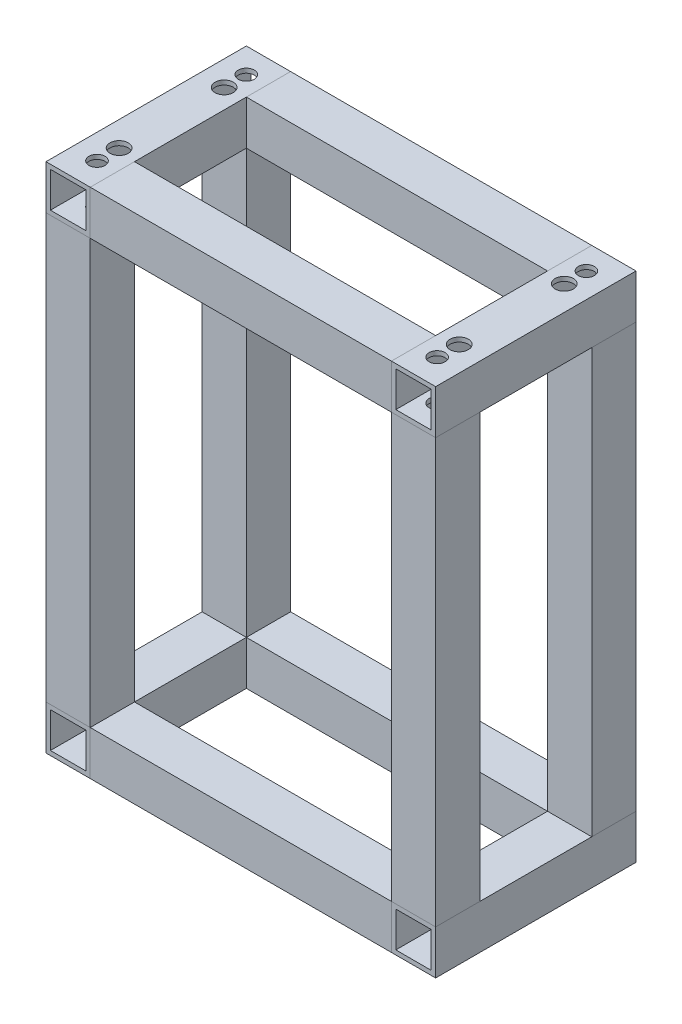
SolidWorks part; units mm, degrees
ref_plane "Front Plane" through (0, 0, 0) normal (0, 0, 1) x (1, 0, 0)
ref_plane "Top Plane" through (0, 0, 0) normal (0, 1, 0) x (1, 0, 0)
ref_plane "Right Plane" through (0, 0, 0) normal (1, 0, 0) x (0, 0, -1)
sketch "Sketch1" plane through (0, 0, 0) normal (0, 1, 0) x (1, 0, 0)
  line L1 (-111.887, 57.531) -> (111.887, 57.531)
  line L2 (-111.887, 57.531) -> (-111.887, -57.531)
  line L3 (-111.887, -57.531) -> (111.887, -57.531)
  line L4 (111.887, 57.531) -> (111.887, -57.531)
  line L5 (-111.887, 57.531) -> (111.887, -57.531) construction
  line L6 (-111.887, -57.531) -> (111.887, 57.531) construction
  point P0 (0, 0)
  dimension "D1" = 115.062
  dimension "D2" = 223.774
sketch "Sketch2" plane through (0, 0, 0) normal (0, 0, 1) x (1, 0, 0)
  line L0 (-111.887, 0) -> (111.887, 0) construction
  line L1 (-111.887, 0) -> (-86.487, 0)
  line L2 (-111.887, 0) -> (-111.887, -25.4)
  line L3 (-111.887, -25.4) -> (-86.487, -25.4)
  line L4 (-86.487, 0) -> (-86.487, -25.4)
  line L5 (-111.887, 0) -> (111.887, 0) construction
  line L6 (0, 0) -> (0, -45.1999) construction
  line L7 (111.887, -25.4) -> (86.487, -25.4)
  line L8 (86.487, 0) -> (86.487, -25.4)
  line L9 (111.887, 0) -> (86.487, 0)
  line L10 (111.887, 0) -> (111.887, -25.4)
  dimension "D1" = 25.4
extrude "Extrude-Thin1" add sketch "Sketch2" along normal mid plane 115.062 thin thin type one direction reverse wall 2.54
sketch "Sketch4" plane through (-86.487, 0, 0) normal (1, 0, 0) x (0, 0, -1)
  line L0 (-57.531, -25.4) -> (57.531, -25.4) construction
  line L1 (-57.531, 0) -> (-32.131, 0)
  line L2 (-57.531, 0) -> (-57.531, -25.4)
  line L3 (-57.531, -25.4) -> (-32.131, -25.4)
  line L4 (-32.131, 0) -> (-32.131, -25.4)
  line L6 (57.531, 0) -> (32.131, 0)
  line L7 (57.531, 0) -> (57.531, -25.4)
  line L8 (57.531, -25.4) -> (32.131, -25.4)
  line L9 (32.131, 0) -> (32.131, -25.4)
extrude "Extrude-Thin2" add sketch "Sketch4" along normal up to surface (172.974 mm away) separate body thin up to face at (86.487, -12.7, 0) thin type one direction reverse wall 2.54
sketch "Sketch5" plane through (0, 0, 57.531) normal (0, 0, 1) x (1, 0, 0)
  line L0 (-111.887, 0) -> (-111.887, -294.132) construction
  line L1 (-111.887, 0) -> (111.887, 0) construction
  line L2 (-111.887, 0) -> (111.887, 0) construction
  dimension "D1" = 294.132
ref_plane "Plane1" through (0, -147.066, 0) normal (0, -1, 0) x (-1, 0, 0)
mirror "Mirror1" about plane through (0, -147.066, 0) normal (0, -1, 0) of bodies 103 101 102 104
sketch "Sketch6" plane through (0, -25.4, 0) normal (0, -1, 0) x (1, 0, 0)
  line L1 (-111.887, 57.531) -> (-86.487, 57.531)
  line L2 (-111.887, 57.531) -> (-111.887, 32.131)
  line L3 (-111.887, 32.131) -> (-86.487, 32.131)
  line L4 (-86.487, 57.531) -> (-86.487, 32.131)
  line L5 (111.887, 57.531) -> (86.487, 57.531)
  line L6 (111.887, 57.531) -> (111.887, 32.131)
  line L7 (111.887, 32.131) -> (86.487, 32.131)
  line L8 (86.487, 57.531) -> (86.487, 32.131)
  line L9 (-86.487, -32.131) -> (-111.887, -32.131)
  line L10 (-86.487, -32.131) -> (-86.487, -57.531)
  line L11 (-86.487, -57.531) -> (-111.887, -57.531)
  line L12 (-111.887, -32.131) -> (-111.887, -57.531)
  line L13 (86.487, -32.131) -> (111.887, -32.131)
  line L14 (86.487, -32.131) -> (86.487, -57.531)
  line L15 (86.487, -57.531) -> (111.887, -57.531)
  line L16 (111.887, -32.131) -> (111.887, -57.531)
extrude "Extrude-Thin3" add sketch "Sketch6" along normal up to surface (243.332 mm away) separate body thin up to face at (-99.187, -268.732, 0) thin type one direction reverse wall 2.54
sketch "Sketch7" plane through (0, 0, 0) normal (0, 1, 0) x (1, 0, 0)
  line L0 (0, 57.531) -> (0, -39.0961) construction
  line L1 (86.487, 57.531) -> (-86.487, 57.531) construction
  arc A0 (-92.4237, 30.5562) -> (-102.9049, 30.5562) centre (-97.6643, 30.5562) ccw construction
  arc A1 (-93.0615, 43.2562) -> (-102.2645, 43.2562) centre (-97.663, 43.2562) ccw construction
  arc A2 (-92.4237, 30.5562) -> (-102.9049, 30.5562) centre (-97.6643, 30.5562) ccw construction
  arc A3 (-93.0615, 43.2562) -> (-102.2645, 43.2562) centre (-97.663, 43.2562) ccw construction
  arc A4 (-93.0615, -42.4688) -> (-102.2645, -42.4688) centre (-97.663, -42.4688) ccw construction
  arc A5 (-102.9049, -29.7688) -> (-92.4237, -29.7688) centre (-97.6643, -29.7688) ccw construction
  arc A6 (-93.0615, -42.4688) -> (-102.2645, -42.4688) centre (-97.663, -42.4688) ccw construction
  arc A7 (-102.9049, -29.7688) -> (-92.4237, -29.7688) centre (-97.6643, -29.7688) ccw construction
  circle A8 centre (-97.663, -42.4688) radius 4.6015
  circle A9 centre (-97.6643, -29.7688) radius 5.2406
  circle A10 centre (-97.6643, 30.5562) radius 5.2406
  circle A11 centre (-97.663, 43.2562) radius 4.6015
  arc A12 (102.9049, -29.7688) -> (92.4237, -29.7688) centre (97.6643, -29.7688) cw construction
  arc A13 (93.0615, -42.4688) -> (102.2645, -42.4688) centre (97.663, -42.4688) cw construction
  arc A14 (93.0615, 43.2562) -> (102.2645, 43.2562) centre (97.663, 43.2562) cw construction
  arc A15 (92.4237, 30.5562) -> (102.9049, 30.5562) centre (97.6643, 30.5562) cw construction
  circle A16 centre (97.663, 43.2562) radius 4.6015
  circle A17 centre (97.6643, 30.5562) radius 5.2406
  circle A18 centre (97.6643, -29.7688) radius 5.2406
  circle A19 centre (97.663, -42.4688) radius 4.6015
extrude "Cut-Extrude1" cut sketch "Sketch7" against normal up to surface (25.4 mm away) up to face at (-99.187, -25.4, 0)
